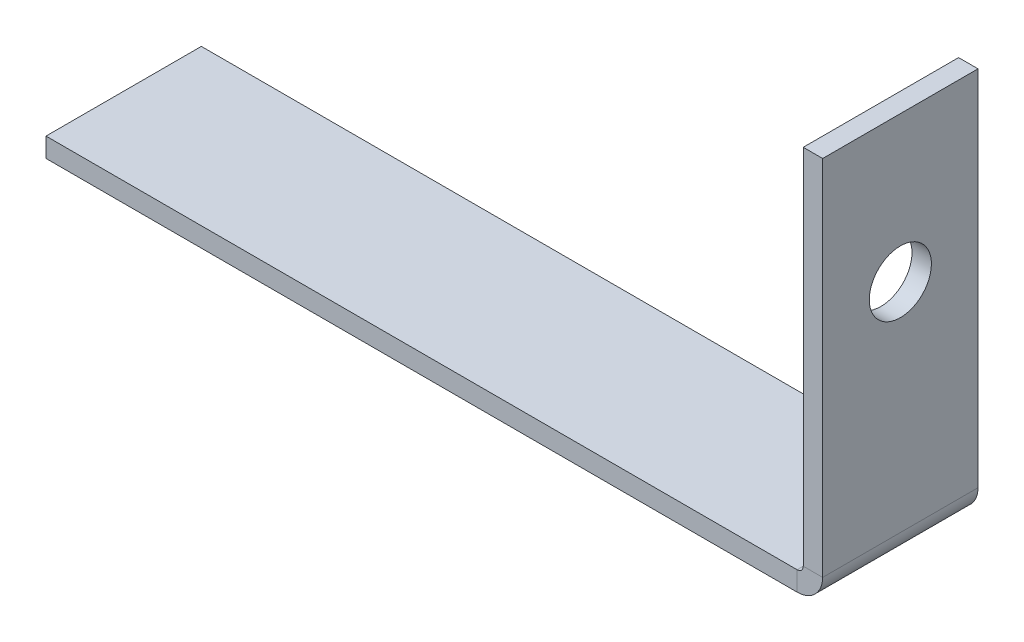
SolidWorks part; units mm, degrees
note: The reader was unsure of these and kept them because the rebuilt part matched: flange length of "Edge-Flange1".
ref_plane "Front Plane" through (0, 0, 0) normal (0, 0, 1) x (1, 0, 0)
ref_plane "Top Plane" through (0, 0, 0) normal (0, 1, 0) x (1, 0, 0)
ref_plane "Right Plane" through (0, 0, 0) normal (1, 0, 0) x (0, 0, -1)
sketch "Sketch2" plane through (0, 0, 0) normal (0, 1, 0) x (1, 0, 0)
  line L1 (0, 0) -> (127, 0)
  line L2 (0, 0) -> (0, 25.4)
  line L3 (0, 25.4) -> (127, 25.4)
  line L4 (127, 0) -> (127, 25.4)
  dimension "D1" = 127
  dimension "2in" = 25.4
base flange "Base-Flange1" sketch "Sketch2" thickness 3.175 reverse thickness direction no parameters "D1"=1
edge flange "Edge-Flange1" sketch "Sketch9" flange angle 90 flange length 63.5 flange position material inside bend radius 1 thickness 3.175 relief rectangular parameters "D6"=10
sketch "Sketch9" plane through (127, 0, 0) normal (1, 0, 0) x (0, 0, -1)
  line L2 (0, 0) -> (0, 60.325)
  line L3 (0, 60.325) -> (25.4, 60.325)
  line L4 (25.4, 60.325) -> (25.4, 0)
  line L7 (0, 0) -> (25.4, 0) construction
  line L8 (0, 0) -> (25.4, 0)
bend "EdgeBend1" bend radius 1 bend angle 90 parameters "D5"=1
sketch "Sketch10" plane through (127, 0, 0) normal (1, 0, 0) x (0, 0, -1)
  line L0 (25.4, 60.325) -> (0, 60.325) construction
  circle A0 centre (12.7, 36.5125) radius 5.08
  arc A1 (23.0592, 29.337) -> (23.0592, 43.688) centre (23.0592, 36.5125) ccw construction
  circle A2 centre (75.1316, 63.5) radius 5.08 construction
  point P5 (30.2347, 36.5125)
  point P8 (12.7, 60.325)
extrude "Cut-Extrude1" cut sketch "Sketch10" against normal up to next normal cut yes
sketch "Bend-Lines1" [suppressed] plane through (0, 0, 0) normal (0, 1, 0) x (1, 0, 0)
sketch "Bounding-Box1" [suppressed] plane through (0, 0, 0) normal (0, 1, 0) x (1, 0, 0)
sheet metal parameters "Sheet-Metal1" thickness 3.175 parameters "D1"=1
flat pattern "Flat-Pattern1" [suppressed]
sketch "Bend-Lines2" plane through (0, 0, 0) normal (0, 1, 0) x (1, 0, 0)
sketch3d "Bounding-Box2" [suppressed]
  line L0 (-133.9121, 39.4719, 0) -> (0, 39.4719, 0) construction
  line L1 (-133.9121, 0, 0) -> (0, 0, 0) construction
  line L2 (-133.9121, 39.4719, 0) -> (-133.9121, 0, 0) construction
  line L3 (0, 39.4719, 0) -> (0, 0, 0) construction
sheet metal parameters "Sheet-Metal2" thickness 3.175 parameters "D1"=1
flat pattern "Flat-Pattern1"
sketch "Bend-Lines2" plane through (0, 0, 0) normal (0, 1, 0) x (1, 0, 0)
  line L0 (124.8572, 0) -> (124.8572, 25.4) construction
  line L1 (124.8572, 0) -> (124.8572, 25.4) construction
sketch3d "Bounding-Box2" [suppressed]
  line L0 (186.2144, 25.4, 0) -> (0, 25.4, 0) construction
  line L1 (186.2144, 0, 0) -> (0, 0, 0) construction
  line L2 (186.2144, 25.4, 0) -> (186.2144, 0, 0) construction
  line L3 (0, 25.4, 0) -> (0, 0, 0) construction
bend of the flat pattern "Flatten-<EdgeBend1>1"
sheet metal parameters "Sheet-Metal3" thickness 3.175 parameters "D1"=1
flat pattern "Flat-Pattern1"
sketch "Bend-Lines2" plane through (0, 0, 0) normal (0, 1, 0) x (1, 0, 0)
  line L0 (124.8572, 0) -> (124.8572, 25.4) construction
  line L1 (124.8572, 0) -> (124.8572, 25.4) construction
sketch3d "Bounding-Box2" [suppressed]
  line L0 (186.2144, 25.4, 0) -> (0, 25.4, 0) construction
  line L1 (186.2144, 0, 0) -> (0, 0, 0) construction
  line L2 (186.2144, 25.4, 0) -> (186.2144, 0, 0) construction
  line L3 (0, 25.4, 0) -> (0, 0, 0) construction
bend of the flat pattern "Flatten-<EdgeBend1>1"
